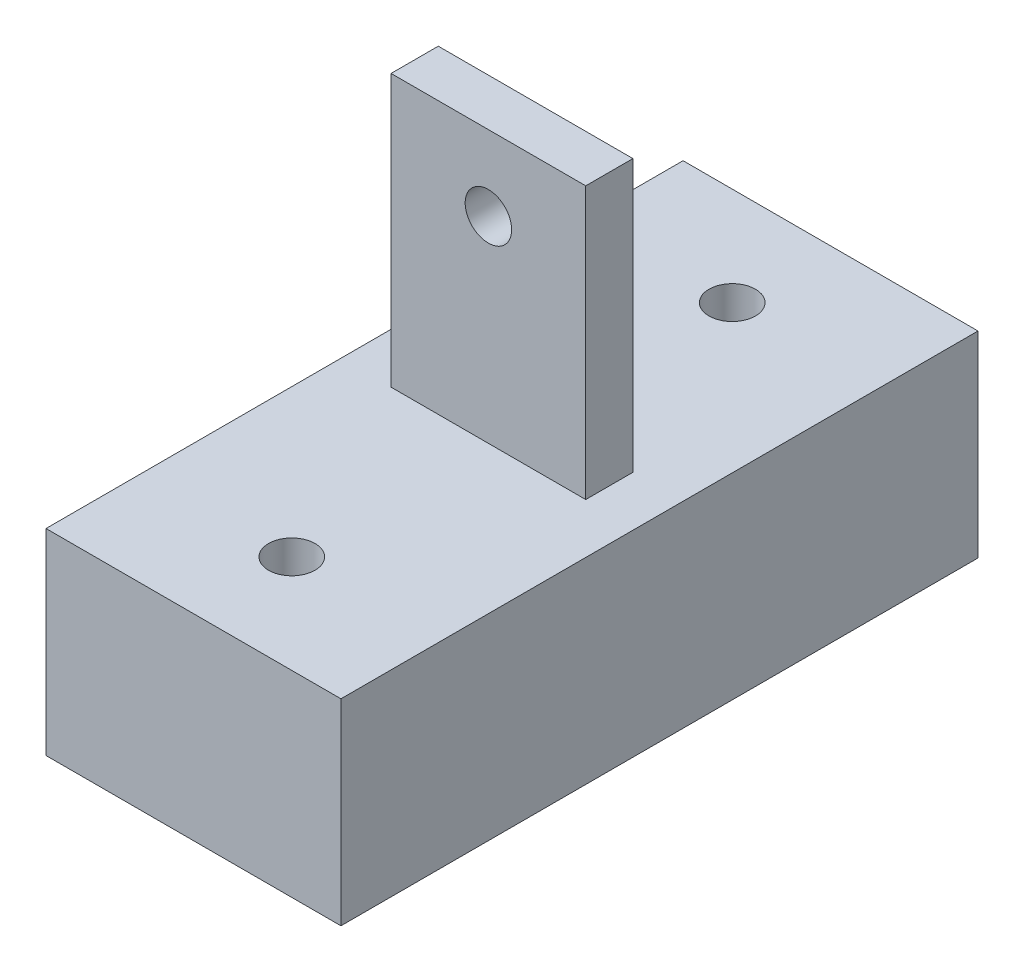
SolidWorks part; units mm, degrees
ref_plane "Front Plane" through (0, 0, 0) normal (0, 0, 1) x (1, 0, 0)
ref_plane "Top Plane" through (0, 0, 0) normal (0, 1, 0) x (1, 0, 0)
ref_plane "Right Plane" through (0, 0, 0) normal (1, 0, 0) x (0, 0, -1)
sketch "Sketch1" plane through (0, 0, 0) normal (1, 0, 0) x (0, 0, -1)
  line L1 (-20.574, 12.7) -> (20.574, 12.7)
  line L2 (-20.574, 12.7) -> (-20.574, 0)
  line L3 (-20.574, 0) -> (20.574, 0)
  line L4 (20.574, 12.7) -> (20.574, 0)
  line L5 (-1.524, 12.7) -> (1.524, 12.7)
  line L6 (-1.524, 12.7) -> (-1.524, 38.1)
  line L7 (-1.524, 38.1) -> (1.524, 38.1)
  line L8 (1.524, 12.7) -> (1.524, 38.1)
  point P8 (0, 0)
  point P10 (0, 38.1)
  point P11 (16.4203, -0.4026)
  point P12 (8.1904, -0.9905)
  point P13 (-3.048, 32.2365)
  point P14 (0, 0)
  dimension "D1" = 12.7
  dimension "D2" = 25.4
  dimension "D3" = 3.048
  dimension "D4" = 19.05
extrude "Boss-Extrude1" add sketch "Sketch1" along normal mid plane 19.05 contours L4 L1 L2 L3 region at (0, 6.35, 0)
extrude "Boss-Extrude2" add sketch "Sketch1<3>" along normal mid plane 12.573 contours L1 L8 L7 L6 region at (0, 25.4, 0)
sketch "Sketch1<3>" plane through (0, 0, 0) normal (1, 0, 0) x (0, 0, -1) same geometry as "Sketch1"
sketch "Sketch2" plane through (0, 0, 1.524) normal (0, 0, 1) x (1, 0, 0)
  line L0 (-6.2865, 19.05) -> (6.2865, 19.05) construction
  line L1 (-6.2865, 12.7) -> (-6.2865, 38.1) construction
  line L2 (6.2865, 12.7) -> (6.2865, 38.1) construction
  line L3 (9.525, 12.7) -> (-9.525, 12.7) construction
  circle A0 centre (0, 25.4) radius 1.5
  circle A1 centre (0, 31.75) radius 1.5
  point P10 (0, 0)
  point P11 (0, 19.05)
  dimension "D3" = 3
  dimension "D1" = 6.35
  dimension "D2" = 6.35
  dimension "D4" = 12.7
extrude "Cut-Extrude1" cut sketch "Sketch2" against normal through all
sketch "Sketch3" plane through (0, 0, 1.524) normal (0, 0, 1) x (1, 0, 0)
  line L0 (6.2865, 12.7) -> (6.2865, 38.1) construction
  line L1 (-6.2865, 38.1) -> (6.2865, 38.1)
  line L2 (-6.2865, 38.1) -> (-6.2865, 30.25)
  line L3 (-6.2865, 30.25) -> (6.2865, 30.25)
  line L4 (6.2865, 38.1) -> (6.2865, 30.25)
  circle A0 centre (0, 31.75) radius 1.5 construction
  point P11 (0, 25.4)
  point P12 (0, 25.4)
extrude "Cut-Extrude2" cut sketch "Sketch3" against normal through all
sketch "Sketch4" plane through (0, 12.7, 0) normal (0, 1, 0) x (1, 0, 0)
  line L0 (0, -14.224) -> (0, 14.224) construction
  line L1 (6.2865, -1.524) -> (-6.2865, -1.524) construction
  circle A0 centre (0, -14.224) radius 1.5
  circle A2 centre (0, 14.224) radius 1.5
  point P2 (0, 0)
  dimension "D1" = 3
  dimension "D2" = 12.7
extrude "Cut-Extrude3" cut sketch "Sketch4" against normal through all
sketch "Sketch5" plane through (0, 0, 0) normal (0, -1, 0) x (1, 0, 0)
  circle A0 centre (0, 14.224) radius 4.7625
  circle A1 centre (0, -14.224) radius 4.7625
  circle A2 centre (0, 14.224) radius 1.5 construction
  circle A3 centre (0, -14.224) radius 1.5 construction
  dimension "D1" = 9.525
extrude "Cut-Extrude4" cut sketch "Sketch5" against normal blind 6.35
